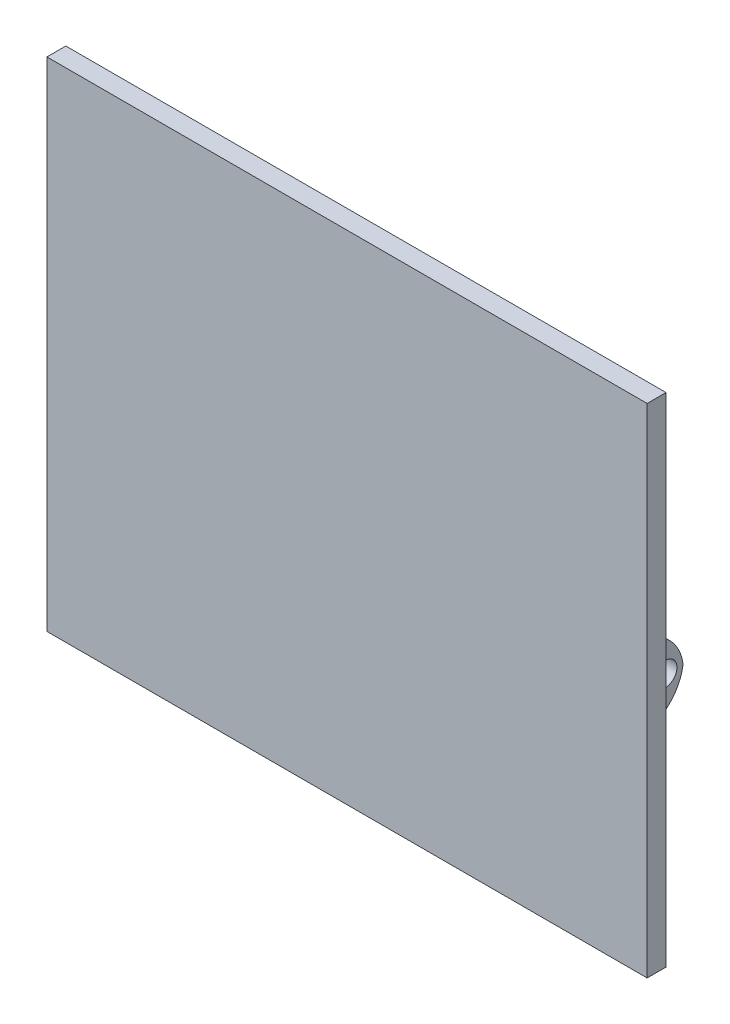
SolidWorks part; units mm, degrees
ref_plane "Front Plane" through (0, 0, 0) normal (0, 0, 1) x (1, 0, 0)
ref_plane "Top Plane" through (0, 0, 0) normal (0, 1, 0) x (1, 0, 0)
ref_plane "Right Plane" through (0, 0, 0) normal (1, 0, 0) x (0, 0, -1)
sketch "Sketch2" plane through (0, 0, 20) normal (0, 0, 1) x (1, 0, 0)
  line L1 (58.065, 80.424) -> (121.572, 80.424)
  line L2 (58.065, 80.424) -> (58.065, 27.78)
  line L3 (58.065, 27.78) -> (121.572, 27.78)
  line L4 (121.572, 80.424) -> (121.572, 27.78)
extrude "Boss-Extrude1" add sketch "Sketch2" along normal blind 2 from offset 5
sketch "Sketch5" plane through (0, 27.78, 0) normal (0, -1, 0) x (1, 0, 0)
  line L1 (58.065, 25) -> (62.565, 25)
  line L2 (58.065, 25) -> (58.065, 21.1559)
  line L3 (58.065, 21.1559) -> (62.565, 21.1559)
  line L4 (62.565, 25) -> (62.565, 21.1559)
  dimension "D1" = 4.5
extrude "Boss-Extrude2" add sketch "Sketch5" against normal blind 52.5
sketch "Sketch8" plane through (58.065, 0, 0) normal (-1, 0, 0) x (0, 0, 1)
  line L0 (27, 80.424) -> (27, 27.78) construction
  line L1 (21.1559, 27.78) -> (24.9959, 27.78)
  line L2 (21.1559, 27.78) -> (21.1559, 32.28)
  line L3 (21.1559, 32.28) -> (24.9959, 32.28)
  line L4 (24.9959, 27.78) -> (24.9959, 32.28)
  dimension "D1" = 4.5
  dimension "D2" = 3.84
  dimension "D3" = 2.0041
extrude "Cut-Extrude1" cut sketch "Sketch8" against normal blind 5
sketch "Sketch9" plane through (58.065, 0, 0) normal (-1, 0, 0) x (0, 0, 1)
  line L0 (21.1559, 80.28) -> (21.1559, 32.28) construction
  line L1 (25, 80.424) -> (21.1559, 80.424)
  line L2 (25, 80.424) -> (25, 75.924)
  line L3 (25, 75.924) -> (21.1559, 75.924)
  line L4 (21.1559, 80.424) -> (21.1559, 75.924)
  dimension "D1" = 4.5
extrude "Cut-Extrude2" cut sketch "Sketch9" against normal blind 5
fillet "Fillet1" radius 1 2 edges at (58.065, 54.102, 21.1559) (62.565, 54.102, 21.1559)
sketch "Sketch10" plane through (121.572, 0, 0) normal (1, 0, 0) x (0, 0, -1)
  line L1 (-25, 75.924) -> (-25, 27.78) construction
  line L3 (-21.1559, 75.924) -> (-21.1559, 32.28) construction
  line L4 (-25, 56.852) -> (-21.1559, 56.852)
  line L5 (-25, 56.852) -> (-25, 48.4243)
  line L6 (-25, 48.4243) -> (-21.1559, 48.4243)
  line L7 (-21.1559, 56.852) -> (-21.1559, 48.4243)
extrude "Boss-Extrude3" add sketch "Sketch10" against normal blind 2.5 from offset 2 offset against normal yes
fillet "Fillet2" radius 5 2 edges at (118.322, 56.852, 21.1559) (118.322, 48.4243, 21.1559)
sketch "Sketch11" plane through (0, 32.28, 0) normal (0, -1, 0) x (-1, 0, 0)
  line L0 (-58.065, -24.9959) -> (-58.065, -22.1559) construction
  line L1 (-62.565, -24.9959) -> (-58.065, -24.9959) construction
  line L2 (-59.065, -21.1559) -> (-61.565, -21.1559) construction
  circle A0 centre (-60.565, -23.2959) radius 1.25
  dimension "D1" = 2.5
  dimension "D2" = 2.5
  dimension "D3" = 1.7
  dimension "D4" = 2.14
  dimension "D5" = 1.7
extrude "Cut-Extrude3" cut sketch "Sketch11" against normal blind 5
sketch "Sketch12" plane through (0, 75.924, 0) normal (0, 1, 0) x (1, 0, 0)
  circle A0 centre (60.565, -23.2959) radius 1.25 construction
  circle A1 centre (60.565, -23.2959) radius 1.25
  circle A2 centre (60.565, -23.2959) radius 1.25
extrude "Cut-Extrude4" cut sketch "Sketch12" against normal blind 5 contours A1 region at (60.565, 75.924, 23.2959)
sketch "Sketch16" plane through (119.572, 0, 0) normal (1, 0, 0) x (0, 0, -1)
  circle A0 centre (-23.1077, 52.6669) radius 1.2602
extrude "Cut-Extrude5" cut sketch "Sketch16" against normal blind 4
